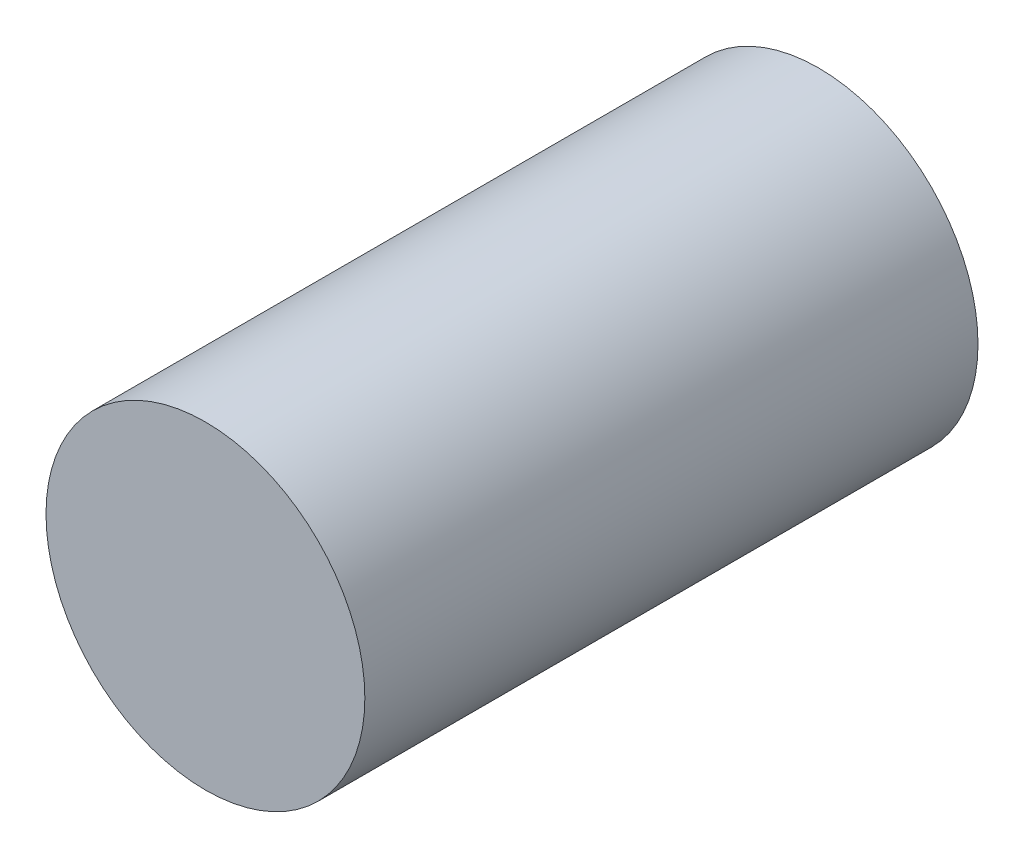
SolidWorks part; units mm, degrees
ref_plane "Plan de face" through (0, 0, 0) normal (0, 0, 1) x (1, 0, 0)
ref_plane "Plan de dessus" through (0, 0, 0) normal (0, 1, 0) x (1, 0, 0)
ref_plane "Plan de droite" through (0, 0, 0) normal (1, 0, 0) x (0, 0, -1)
sketch "Esquisse1" plane through (0, 0, 0) normal (0, 0, 1) x (1, 0, 0)
  circle A0 centre (0, 0) radius 13
  dimension "D1" = 26
extrude "Boss.-Extru.1" add sketch "Esquisse1" against normal blind 50
